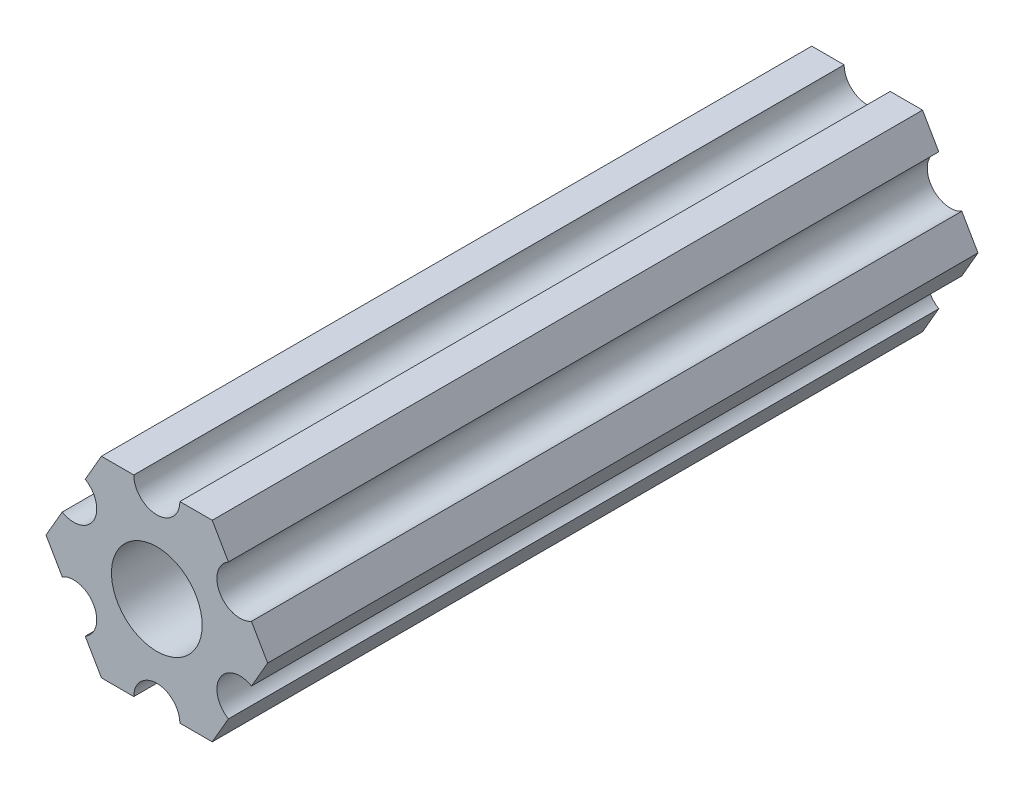
SolidWorks part; units mm, degrees
ref_plane "Plano frontal" through (0, 0, 0) normal (0, 0, 1) x (1, 0, 0)
ref_plane "Plano superior" through (0, 0, 0) normal (0, 1, 0) x (1, 0, 0)
ref_plane "Plano direito" through (0, 0, 0) normal (1, 0, 0) x (0, 0, -1)
sketch "Esboço1" plane through (0, 0, 0) normal (0, 0, 1) x (1, 0, 0)
  line L1 (3.6662, 6.35) -> (-3.6662, 6.35)
  line L2 (-3.6662, 6.35) -> (-7.3323, 0)
  line L3 (-7.3323, 0) -> (-3.6662, -6.35)
  line L4 (-3.6662, -6.35) -> (3.6662, -6.35)
  line L5 (3.6662, -6.35) -> (7.3323, 0)
  line L6 (7.3323, 0) -> (3.6662, 6.35)
  circle A0 centre (0, 0) radius 6.35 construction
  circle A1 centre (0, 0) radius 3
  circle A2 centre (0, 6.35) radius 1.524
  circle A3 centre (5.4993, 3.175) radius 1.524
  circle A4 centre (5.4993, -3.175) radius 1.524
  circle A5 centre (0, -6.35) radius 1.524
  circle A6 centre (-5.4993, -3.175) radius 1.524
  circle A7 centre (-5.4993, 3.175) radius 1.524
  point P24 (0, 0)
  dimension "D1" = 12.7
  dimension "D2" = 6
  dimension "D3" = 3.048
  dimension "D4" = 6
extrude "Ressalto-extrusão1" add sketch "Esboço1" along normal blind 47 contours A7 L2 L3 A6 L4 A5 L5 A4 L6 A3 L1 A2 A1 region at (4.0337, 5.3254, 0)
